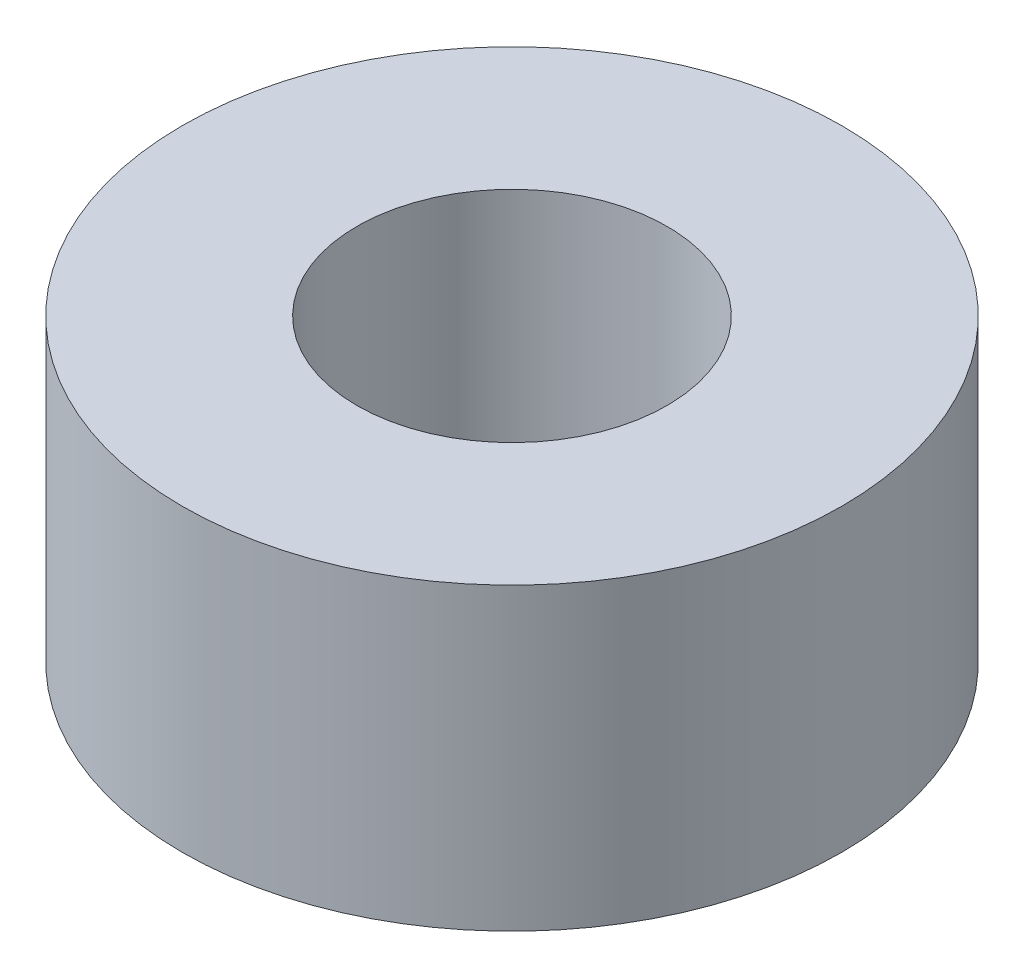
SolidWorks part; units mm, degrees
ref_plane "Front Plane" through (0, 0, 0) normal (0, 0, 1) x (1, 0, 0)
ref_plane "Top Plane" through (0, 0, 0) normal (0, 1, 0) x (1, 0, 0)
ref_plane "Right Plane" through (0, 0, 0) normal (1, 0, 0) x (0, 0, -1)
sketch "Sketch1" plane through (0, 0, 0) normal (0, 1, 0) x (1, 0, 0)
  circle A0 centre (0, 0) radius 2.2
  circle A1 centre (0, 0) radius 4.675
  dimension "D1" = 4.4
  dimension "D2" = 9.35
extrude "Boss-Extrude1" add sketch "Sketch1" along normal blind 4.25
